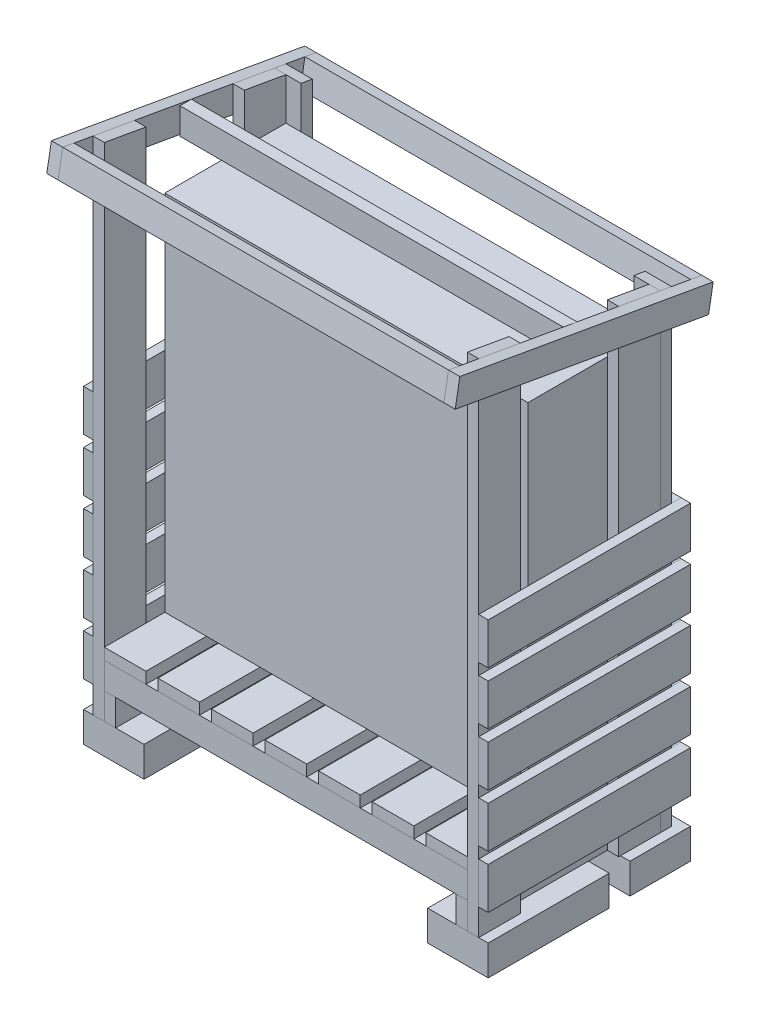
SolidWorks part; units mm, degrees
other "Wood"
ref_plane "Front Plane" through (0, 0, 0) normal (0, 0, 1) x (1, 0, 0)
ref_plane "Top Plane" through (0, 0, 0) normal (0, 1, 0) x (1, 0, 0)
ref_plane "Right Plane" through (0, 0, 0) normal (1, 0, 0) x (0, 0, -1)
sketch "Sketch4" plane through (0, 0, 0) normal (0, 1, 0) x (1, 0, 0)
  line L0 (-609.6, 304.8) -> (609.6, -304.8) construction
  line L1 (-609.6, 304.8) -> (609.6, 304.8)
  line L2 (-609.6, 304.8) -> (-609.6, 266.7)
  line L3 (-609.6, 266.7) -> (609.6, 266.7)
  line L4 (609.6, 304.8) -> (609.6, 266.7)
  line L5 (-609.6, -266.7) -> (609.6, -266.7)
  line L6 (-609.6, -266.7) -> (-609.6, -304.8)
  line L7 (-609.6, -304.8) -> (609.6, -304.8)
  line L8 (609.6, -266.7) -> (609.6, -304.8)
  line L10 (609.6, 304.8) -> (571.5, 304.8)
  line L11 (609.6, 304.8) -> (609.6, -304.8)
  line L12 (609.6, -304.8) -> (571.5, -304.8)
  line L13 (571.5, 304.8) -> (571.5, -304.8)
  line L14 (-609.6, 304.8) -> (-571.5, 304.8)
  line L15 (-609.6, 304.8) -> (-609.6, -304.8)
  line L16 (-609.6, -304.8) -> (-571.5, -304.8)
  line L17 (-571.5, 304.8) -> (-571.5, -304.8)
  point P8 (0, 0)
  dimension "D1" = 609.6
  dimension "D2" = 38.1
  dimension "D3" = 1219.2
sketch "Sketch5" plane through (0, 0, 0) normal (0, 1, 0) x (1, 0, 0)
  line L0 (-609.6, 304.8) -> (-571.5, 304.8) construction
  line L1 (-609.6, -304.8) -> (-571.5, -304.8) construction
  line L2 (609.6, -304.8) -> (571.5, -304.8) construction
  line L3 (609.6, 304.8) -> (571.5, 304.8) construction
  line L4 (609.6, 304.8) -> (609.6, -304.8) construction
  line L5 (571.5, 304.8) -> (571.5, -304.8) construction
  line L6 (-609.6, 304.8) -> (-609.6, -304.8) construction
  line L7 (-571.5, 304.8) -> (-571.5, -304.8) construction
  line L8 (-609.6, 304.8) -> (-571.5, 304.8)
  line L9 (-609.6, -304.8) -> (-571.5, -304.8)
  line L10 (609.6, -304.8) -> (571.5, -304.8)
  line L11 (609.6, 304.8) -> (571.5, 304.8)
  line L12 (609.6, 304.8) -> (609.6, -304.8)
  line L13 (571.5, 304.8) -> (571.5, -304.8)
  line L14 (-609.6, 304.8) -> (-609.6, -304.8)
  line L15 (-571.5, 304.8) -> (-571.5, -304.8)
extrude "Boss-Extrude2" add sketch "Sketch5" against normal blind 88.9
sketch "Sketch6" plane through (0, 0, 0) normal (0, 1, 0) x (1, 0, 0)
  line L0 (-609.6, -266.7) -> (-609.6, -304.8) construction
  line L1 (-609.6, -304.8) -> (609.6, -304.8) construction
  line L2 (-609.6, -266.7) -> (609.6, -266.7) construction
  line L3 (609.6, -266.7) -> (609.6, -304.8) construction
  line L4 (609.6, 304.8) -> (609.6, 266.7) construction
  line L5 (-609.6, 304.8) -> (-609.6, 266.7) construction
  line L6 (-609.6, 266.7) -> (609.6, 266.7) construction
  line L7 (-609.6, 304.8) -> (609.6, 304.8) construction
  line L8 (-609.6, -266.7) -> (-609.6, -304.8)
  line L9 (-609.6, -304.8) -> (609.6, -304.8)
  line L10 (-609.6, -266.7) -> (609.6, -266.7)
  line L11 (609.6, -266.7) -> (609.6, -304.8)
  line L12 (609.6, 304.8) -> (609.6, 266.7)
  line L13 (-609.6, 304.8) -> (-609.6, 266.7)
  line L14 (-609.6, 266.7) -> (609.6, 266.7)
  line L15 (-609.6, 304.8) -> (609.6, 304.8)
extrude "Boss-Extrude3" add sketch "Sketch6" along normal blind 88.9 separate body
sketch "Sketch7" plane through (0, 88.9, 0) normal (0, 1, 0) x (1, 0, 0)
  line L0 (-609.6, -304.8) -> (609.6, -304.8) construction
  line L1 (-609.6, 304.8) -> (-469.9, 304.8)
  line L2 (-609.6, 304.8) -> (-609.6, -304.8)
  line L3 (-609.6, -304.8) -> (-469.9, -304.8)
  line L4 (-469.9, 304.8) -> (-469.9, -304.8)
  line L5 (-429.6918, 304.8) -> (-289.9918, 304.8)
  line L6 (-429.6918, 304.8) -> (-429.6918, -304.8)
  line L7 (-429.6918, -304.8) -> (-289.9918, -304.8)
  line L8 (-289.9918, 304.8) -> (-289.9918, -304.8)
  line L9 (-249.7836, 304.8) -> (-110.0836, 304.8)
  line L10 (-249.7836, 304.8) -> (-249.7836, -304.8)
  line L11 (-249.7836, -304.8) -> (-110.0836, -304.8)
  line L12 (-110.0836, 304.8) -> (-110.0836, -304.8)
  line L13 (-69.8754, 304.8) -> (69.8246, 304.8)
  line L14 (-69.8754, 304.8) -> (-69.8754, -304.8)
  line L15 (-69.8754, -304.8) -> (69.8246, -304.8)
  line L16 (69.8246, 304.8) -> (69.8246, -304.8)
  line L17 (110.0328, 304.8) -> (249.7328, 304.8)
  line L18 (110.0328, 304.8) -> (110.0328, -304.8)
  line L19 (110.0328, -304.8) -> (249.7328, -304.8)
  line L20 (249.7328, 304.8) -> (249.7328, -304.8)
  line L21 (289.941, 304.8) -> (429.641, 304.8)
  line L22 (289.941, 304.8) -> (289.941, -304.8)
  line L23 (289.941, -304.8) -> (429.641, -304.8)
  line L24 (429.641, 304.8) -> (429.641, -304.8)
  line L25 (469.8492, 304.8) -> (609.5492, 304.8)
  line L26 (469.8492, 304.8) -> (469.8492, -304.8)
  line L27 (469.8492, -304.8) -> (609.5492, -304.8)
  line L28 (609.5492, 304.8) -> (609.5492, -304.8)
  line L29 (-609.6, 304.8) -> (-429.6918, 304.8) construction
  dimension "D1" = 139.7
  dimension "D3" = 179.9082
  dimension "D2" = 7
extrude "Boss-Extrude4" add sketch "Sketch7" along normal blind 38.1 separate body
sketch "Sketch10" plane through (0, -88.9, 0) normal (0, -1, 0) x (1, 0, 0)
  line L1 (-609.6, 304.8) -> (-647.7, 304.8)
  line L2 (-609.6, 304.8) -> (-609.6, 165.1)
  line L3 (-609.6, 165.1) -> (-647.7, 165.1)
  line L4 (-647.7, 304.8) -> (-647.7, 165.1)
  line L5 (-609.6, -304.8) -> (-647.7, -304.8)
  line L6 (-609.6, -304.8) -> (-609.6, -165.1)
  line L7 (-609.6, -165.1) -> (-647.7, -165.1)
  line L8 (-647.7, -304.8) -> (-647.7, -165.1)
  line L9 (609.6, 304.8) -> (647.7, 304.8)
  line L10 (609.6, 304.8) -> (609.6, 165.1)
  line L11 (609.6, 165.1) -> (647.7, 165.1)
  line L12 (647.7, 304.8) -> (647.7, 165.1)
  line L13 (609.6, -304.8) -> (647.7, -304.8)
  line L14 (609.6, -304.8) -> (609.6, -165.1)
  line L15 (609.6, -165.1) -> (647.7, -165.1)
  line L16 (647.7, -304.8) -> (647.7, -165.1)
  dimension "D1" = 38.1
  dimension "D2" = 139.7
extrude "Boss-Extrude7" add sketch "Sketch10" against normal blind 1828.8 separate body
sketch "Sketch16" plane through (0, -88.9, 0) normal (0, -1, 0) x (1, 0, 0)
  line L1 (-647.7, -304.8) -> (-558.8, -304.8)
  line L2 (-647.7, -304.8) -> (-647.7, -342.9)
  line L3 (-647.7, -342.9) -> (-558.8, -342.9)
  line L4 (-558.8, -304.8) -> (-558.8, -342.9)
  line L5 (647.7, -304.8) -> (558.8, -304.8)
  line L6 (647.7, -304.8) -> (647.7, -342.9)
  line L7 (647.7, -342.9) -> (558.8, -342.9)
  line L8 (558.8, -304.8) -> (558.8, -342.9)
  dimension "D1" = 38.1
  dimension "D2" = 88.9
extrude "Boss-Extrude11" add sketch "Sketch16" against normal blind 1828.8 separate body
sketch "Sketch12" plane through (0, 127, 0) normal (0, 1, 0) x (1, 0, 0)
  line L0 (609.5492, -304.8) -> (609.5492, 304.8) construction
  line L1 (-609.6, 304.8) -> (609.5492, 304.8)
  line L2 (-609.6, 304.8) -> (-609.6, -101.6)
  line L3 (-609.6, -101.6) -> (609.5492, -101.6)
  line L4 (609.5492, 304.8) -> (609.5492, -101.6)
  dimension "D1" = 406.4
extrude "Boss-Extrude8" add sketch "Sketch12" along normal blind 1219.2 separate body
sketch "Sketch13" plane through (647.7, 0, 0) normal (1, 0, 0) x (0, 0, -1)
  line L0 (-101.6, 1346.2) -> (304.8, 1346.2) construction
  line L1 (-101.6, 1346.2) -> (304.8, 1346.2) construction
  line L2 (429.0627, 1375.0891) -> (-421.8373, 1525.1258)
  line L3 (-304.8, 1739.9) -> (-304.8, -88.9) construction
  line L6 (-406.4, 1612.6752) -> (444.5, 1462.6385)
  line L8 (-406.4, 1612.6752) -> (-421.8373, 1525.1258)
  line L9 (304.8, 1739.9) -> (304.8, -88.9) construction
  line L10 (444.5, 1462.6385) -> (429.0627, 1375.0891)
  line L11 (304.8, 1739.9) -> (304.8, -88.9) construction
  point P6 (304.8, 1397)
  point P7 (0, 0)
  dimension "D1" = 88.9
  dimension "D2" = 50.8
  dimension "D3" = 10
  dimension "D4" = 101.6
  dimension "D5" = 139.7
  dimension "D6" = 864.0265
extrude "Boss-Extrude9" add sketch "Sketch13" along normal blind 38.1 separate body
mirror "Mirror1" about plane through (0, 0, 0) normal (1, 0, 0) of bodies 126
sketch "Sketch14" plane through (647.7, 0, 0) normal (1, 0, 0) x (0, 0, -1)
  line L13 (-304.8, 1739.9) -> (-304.8, 1594.7604)
  line L14 (-304.8, 1739.9) -> (-304.8, -88.9) construction
  line L15 (444.5, 1462.6385) -> (-406.4, 1612.6752) construction
  line L16 (-304.8, 1594.7604) -> (342.9, 1480.5534)
  line L17 (342.9, 1739.9) -> (342.9, -88.9) construction
  line L18 (342.9, 1480.5534) -> (342.9, 1739.9)
  line L19 (342.9, 1739.9) -> (-304.8, 1739.9)
extrude "Cut-Extrude1" cut sketch "Sketch14" against normal through all
sketch "Sketch15" plane through (-647.7, 0, 0) normal (1, 0, 0) x (0, 0, -1)
  line L0 (-406.4, 1612.6752) -> (-421.8373, 1525.1258)
  line L1 (-421.8373, 1525.1258) -> (-384.3161, 1518.5098)
  line L2 (-421.8373, 1525.1258) -> (429.0627, 1375.0891) construction
  line L3 (-384.3161, 1518.5098) -> (-368.8788, 1606.0592)
  line L4 (444.5, 1462.6385) -> (-406.4, 1612.6752) construction
  line L5 (-368.8788, 1606.0592) -> (-406.4, 1612.6752)
  line L6 (444.5, 1462.6385) -> (406.9788, 1469.2545)
  line L7 (406.9788, 1469.2545) -> (391.5415, 1381.7051)
  line L8 (391.5415, 1381.7051) -> (429.0627, 1375.0891)
  line L9 (429.0627, 1375.0891) -> (444.5, 1462.6385) construction
  line L10 (429.0627, 1375.0891) -> (444.5, 1462.6385)
  line L21 (25.4, 1536.5372) -> (-12.7, 1536.5372)
  line L22 (25.4, 1536.5372) -> (25.4, 1447.6372)
  line L23 (25.4, 1447.6372) -> (-12.7, 1447.6372)
  line L24 (-12.7, 1536.5372) -> (-12.7, 1447.6372)
  dimension "D1" = 38.1
  dimension "D2" = 152.4
extrude "Boss-Extrude10" add sketch "Sketch15" along normal up to surface (1295.4 mm away) separate body up to face at (647.7, 1493.8822, -11.3313)
sketch "Sketch18" plane through (0, 0, -342.9) normal (0, 0, -1) x (-1, 0, 0)
  line L0 (-647.7, 1480.5534) -> (-647.7, -88.9) construction
  line L1 (-647.7, 0) -> (647.7, 0)
  line L2 (-647.7, 0) -> (-647.7, 139.7)
  line L3 (-647.7, 139.7) -> (647.7, 139.7)
  line L4 (647.7, 0) -> (647.7, 139.7)
  line L5 (647.7, 1480.5534) -> (647.7, -88.9) construction
  line L25 (-558.8, -88.9) -> (-647.7, -88.9) construction
  line L26 (-647.7, 177.8) -> (647.7, 177.8)
  line L27 (-647.7, 177.8) -> (-647.7, 317.5)
  line L28 (-647.7, 317.5) -> (647.7, 317.5)
  line L29 (647.7, 177.8) -> (647.7, 317.5)
  line L30 (-647.7, 355.6) -> (647.7, 355.6)
  line L31 (-647.7, 355.6) -> (-647.7, 495.3)
  line L32 (-647.7, 495.3) -> (647.7, 495.3)
  line L33 (647.7, 355.6) -> (647.7, 495.3)
  line L34 (-647.7, 533.4) -> (647.7, 533.4)
  line L35 (-647.7, 533.4) -> (-647.7, 673.1)
  line L36 (-647.7, 673.1) -> (647.7, 673.1)
  line L37 (647.7, 533.4) -> (647.7, 673.1)
  line L38 (-647.7, 711.2) -> (647.7, 711.2)
  line L39 (-647.7, 711.2) -> (-647.7, 850.9)
  line L40 (-647.7, 850.9) -> (647.7, 850.9)
  line L41 (647.7, 711.2) -> (647.7, 850.9)
  line L42 (-647.7, 0) -> (-647.7, 177.8) construction
  dimension "D1" = 139.7
  dimension "D3" = 88.9
  dimension "D4" = 177.8
  dimension "D2" = 5
extrude "Boss-Extrude12" add sketch "Sketch18" along normal blind 31.75 separate body
sketch "Sketch20" plane through (647.7, 0, 0) normal (1, 0, 0) x (0, 0, -1)
  line L0 (-304.8, 1594.7604) -> (-304.8, -88.9) construction
  line L1 (374.65, 139.7) -> (-304.8, 139.7)
  line L2 (374.65, 139.7) -> (374.65, 0)
  line L3 (374.65, 0) -> (-304.8, 0)
  line L4 (-304.8, 139.7) -> (-304.8, 0)
  line L5 (374.65, 711.2) -> (342.9, 711.2) construction
  line L6 (374.65, 317.5) -> (-304.8, 317.5)
  line L7 (374.65, 317.5) -> (374.65, 177.8)
  line L8 (374.65, 177.8) -> (-304.8, 177.8)
  line L9 (-304.8, 317.5) -> (-304.8, 177.8)
  line L10 (374.65, 495.3) -> (-304.8, 495.3)
  line L11 (374.65, 495.3) -> (374.65, 355.6)
  line L12 (374.65, 355.6) -> (-304.8, 355.6)
  line L13 (-304.8, 495.3) -> (-304.8, 355.6)
  line L14 (374.65, 673.1) -> (-304.8, 673.1)
  line L15 (374.65, 673.1) -> (374.65, 533.4)
  line L16 (374.65, 533.4) -> (-304.8, 533.4)
  line L17 (-304.8, 673.1) -> (-304.8, 533.4)
  line L18 (374.65, 850.9) -> (-304.8, 850.9)
  line L19 (374.65, 850.9) -> (374.65, 711.2)
  line L20 (374.65, 711.2) -> (-304.8, 711.2)
  line L21 (-304.8, 850.9) -> (-304.8, 711.2)
  line L22 (374.65, 533.4) -> (342.9, 533.4) construction
  line L23 (374.65, 355.6) -> (342.9, 355.6) construction
  line L24 (374.65, 177.8) -> (342.9, 177.8) construction
extrude "Boss-Extrude13" add sketch "Sketch20" along normal blind 31.75 separate body
mirror "Mirror2" about plane through (0, 0, 0) normal (1, 0, 0) of bodies 153 152 151 150 149
sketch "Sketch21" plane through (0, -88.9, 0) normal (0, -1, 0) x (1, 0, 0)
  line L1 (-679.45, 304.8) -> (-476.25, 304.8)
  line L2 (-679.45, 304.8) -> (-679.45, -101.6)
  line L3 (-679.45, -101.6) -> (-476.25, -101.6)
  line L4 (-476.25, 304.8) -> (-476.25, -101.6)
  line L5 (679.45, 304.8) -> (476.25, 304.8)
  line L6 (679.45, 304.8) -> (679.45, -101.6)
  line L7 (679.45, -101.6) -> (476.25, -101.6)
  line L8 (476.25, 304.8) -> (476.25, -101.6)
  line L9 (-679.45, -374.65) -> (-273.05, -374.65)
  line L10 (-679.45, -374.65) -> (-679.45, -171.45)
  line L11 (-679.45, -171.45) -> (-273.05, -171.45)
  line L12 (-273.05, -374.65) -> (-273.05, -171.45)
  line L13 (679.45, -374.65) -> (273.05, -374.65)
  line L14 (679.45, -374.65) -> (679.45, -171.45)
  line L15 (679.45, -171.45) -> (273.05, -171.45)
  line L16 (273.05, -374.65) -> (273.05, -171.45)
  dimension "D1" = 203.2
  dimension "D2" = 406.4
extrude "Boss-Extrude14" add sketch "Sketch21" along normal blind 101.6 separate body
